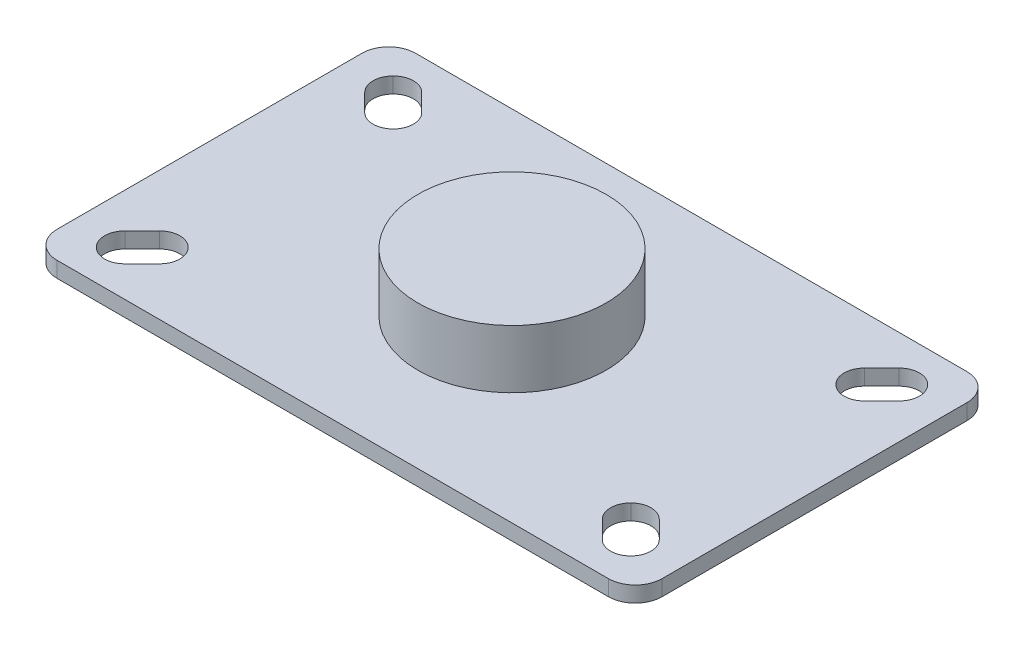
SolidWorks part; units mm, degrees
ref_plane "Front Plane" through (0, 0, 0) normal (0, 0, 1) x (1, 0, 0)
ref_plane "Top Plane" through (0, 0, 0) normal (0, 1, 0) x (1, 0, 0)
ref_plane "Right Plane" through (0, 0, 0) normal (1, 0, 0) x (0, 0, -1)
sketch "Sketch1" plane through (0, 0, 0) normal (0, 1, 0) x (1, 0, 0)
  line L1 (-67.5, 40) -> (67.5, 40)
  line L2 (-67.5, 40) -> (-67.5, -40)
  line L3 (-67.5, -40) -> (67.5, -40)
  line L4 (67.5, 40) -> (67.5, -40)
  line L5 (-67.5, 40) -> (67.5, -40) construction
  line L6 (-67.5, -40) -> (67.5, 40) construction
  point P0 (0, 0)
extrude "Boss-Extrude1" add sketch "Sketch1" along normal blind 3.5
sketch "Sketch2" plane through (0, 3.5, 0) normal (0, 1, 0) x (1, 0, 0)
  circle A0 centre (0, 0) radius 21
extrude "Boss-Extrude2" add sketch "Sketch2" along normal blind 13
sketch "Sketch4" plane through (0, 3.5, 0) normal (0, 1, 0) x (1, 0, 0)
  line L0 (46.1915, -26.0555) -> (56.4445, -36.3085)
  line L1 (46.1915, -26.0555) -> (52.5555, -19.6915)
  line L2 (56.4445, -36.3085) -> (62.8085, -29.9445)
  line L3 (52.5555, -19.6915) -> (62.8085, -29.9445)
  line L4 (46.1915, -26.0555) -> (62.8085, -29.9445) construction
  line L5 (56.4445, -36.3085) -> (52.5555, -19.6915) construction
  line L6 (-67.5, -40) -> (67.5, -40) construction
  line L7 (67.5, -40) -> (67.5, 40) construction
  line L8 (-56.4445, 36.3085) -> (-46.1915, 26.0555)
  line L9 (-62.8085, 29.9445) -> (-52.5555, 19.6915)
  line L10 (-52.5555, 19.6915) -> (-56.4445, 36.3085) construction
  line L11 (-52.5555, 19.6915) -> (-46.1915, 26.0555)
  line L12 (-62.8085, 29.9445) -> (-46.1915, 26.0555) construction
  line L13 (-62.8085, 29.9445) -> (-56.4445, 36.3085)
  line L16 (67.5, 40) -> (-67.5, 40) construction
  line L17 (-67.5, 40) -> (-67.5, -40) construction
  line L18 (62.8085, 29.9445) -> (46.1915, 26.0555) construction
  line L19 (62.8085, 29.9445) -> (56.4445, 36.3085)
  line L20 (52.5555, 19.6915) -> (56.4445, 36.3085) construction
  line L21 (52.5555, 19.6915) -> (46.1915, 26.0555)
  line L22 (46.1915, 26.0555) -> (56.4445, 36.3085)
  line L23 (52.5555, 19.6915) -> (62.8085, 29.9445)
  line L24 (-62.8085, -29.9445) -> (-52.5555, -19.6915)
  line L25 (-46.1915, -26.0555) -> (-62.8085, -29.9445) construction
  line L26 (-46.1915, -26.0555) -> (-52.5555, -19.6915)
  line L27 (-56.4445, -36.3085) -> (-46.1915, -26.0555)
  line L28 (-56.4445, -36.3085) -> (-62.8085, -29.9445)
  line L29 (-56.4445, -36.3085) -> (-52.5555, -19.6915) construction
  point P1 (54.5, -28)
  point P9 (-54.5, 28)
  point P18 (54.5, 28)
  point P23 (-54.5, -28)
  dimension "D1" = 12
  dimension "D2" = 13
  dimension "D3" = 45
  dimension "D4" = 12
  dimension "D5" = 13
extrude "Cut-Extrude1" cut sketch "Sketch4" against normal through all
fillet "Fillet1" radius 6 4 edges at (-67.5, 1.75, 40) (-67.5, 1.75, -40) (67.5, 1.75, -40) (67.5, 1.75, 40)
fillet "Fillet2" radius 4.5 16 edges at (56.4445, 1.75, -36.3085) (52.5555, 1.75, 19.6915) (46.1915, 1.75, -26.0555) (46.1915, 1.75, 26.0555) (52.5555, 1.75, -19.6915) (56.4445, 1.75, 36.3085) (62.8085, 1.75, -29.9445) (62.8085, 1.75, 29.9445) (-52.5555, 1.75, 19.6915) (-46.1915, 1.75, 26.0555) (-46.1915, 1.75, -26.0555) (-52.5555, 1.75, -19.6915) (-56.4445, 1.75, 36.3085) (-62.8085, 1.75, 29.9445) (-62.8085, 1.75, -29.9445) (-56.4445, 1.75, -36.3085)
